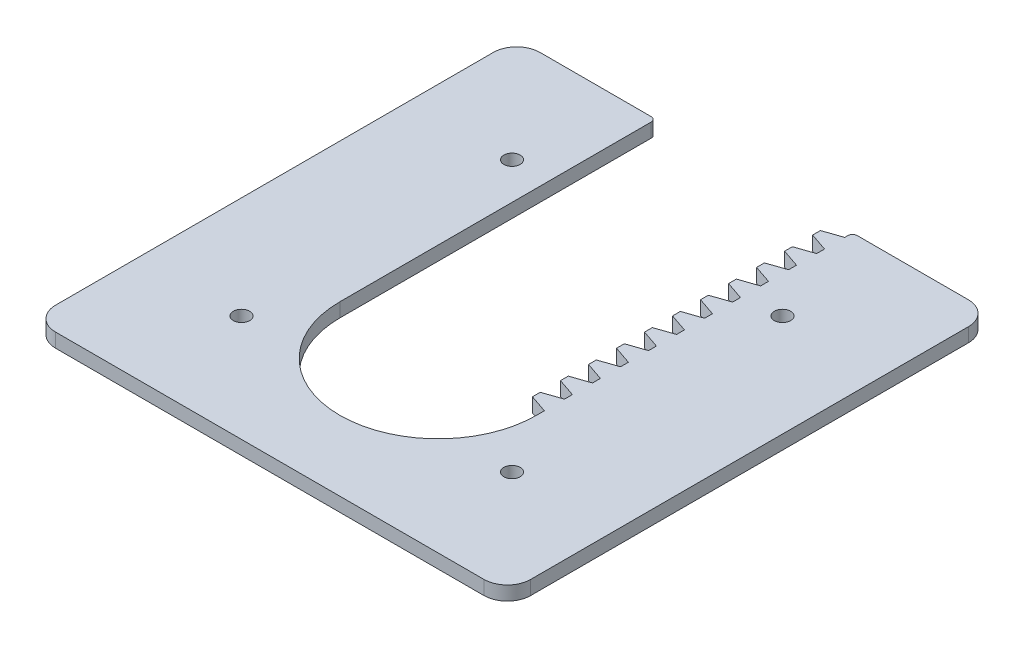
SolidWorks part; units mm, degrees
ref_plane "Front Plane" through (0, 0, 0) normal (0, 0, 1) x (1, 0, 0)
ref_plane "Top Plane" through (0, 0, 0) normal (0, 1, 0) x (1, 0, 0)
ref_plane "Right Plane" through (0, 0, 0) normal (1, 0, 0) x (0, 0, -1)
sketch "Sketch1" plane through (0, 0, 0) normal (0, 1, 0) x (1, 0, 0)
  line L0 (0, 0) -> (0, 21) construction
  line L1 (17.1887, 0) -> (0, 0) construction
  line L2 (21.0585, 3.843) -> (17.1887, 5.1665) construction
  line L3 (17.1887, 5.1665) -> (17.1887, 6.8335) construction
  line L4 (17.1887, 6.8335) -> (21.0585, 8.157) construction
  line L5 (21.0585, 9.843) -> (21.0585, 8.157) construction
  line L6 (21.0585, 9.843) -> (17.1887, 11.1665) construction
  line L7 (17.1887, 11.1665) -> (17.1887, 12.8335) construction
  line L8 (17.1887, 12.8335) -> (21.0585, 14.157) construction
  line L9 (21.0585, 15.843) -> (21.0585, 14.157) construction
  line L10 (21.0585, 15.843) -> (17.1887, 17.1665) construction
  line L11 (17.1887, 17.1665) -> (17.1887, 18.8335) construction
  line L12 (17.1887, 18.8335) -> (21.0585, 20.157) construction
  line L13 (21.0585, 21.843) -> (21.0585, 20.157) construction
  line L14 (21.0585, 21.843) -> (17.1887, 23.1665) construction
  line L15 (17.1887, 23.1665) -> (17.1887, 24.8335) construction
  line L16 (17.1887, 24.8335) -> (21.0585, 26.157) construction
  line L17 (21.0585, 27.843) -> (21.0585, 26.157) construction
  line L18 (21.0585, 27.843) -> (17.1887, 29.1665) construction
  line L19 (17.1887, 29.1665) -> (17.1887, 30.8335) construction
  line L20 (17.1887, 30.8335) -> (21.0585, 32.157) construction
  line L21 (21.0585, 33.843) -> (21.0585, 32.157) construction
  line L22 (21.0585, 33.843) -> (17.1887, 35.1665) construction
  line L23 (17.1887, 35.1665) -> (17.1887, 36.8335) construction
  line L24 (17.1887, 36.8335) -> (21.0585, 38.157) construction
  line L25 (21.0585, 39.843) -> (21.0585, 38.157) construction
  line L26 (21.0585, 39.843) -> (17.1887, 41.1665) construction
  line L27 (17.1887, 41.1665) -> (17.1887, 42.8335) construction
  line L28 (17.1887, 42.8335) -> (21.0585, 44.157) construction
  line L29 (21.0585, 45.843) -> (21.0585, 44.157) construction
  line L30 (21.0585, 45.843) -> (17.1887, 47.1665) construction
  line L31 (17.1887, 47.1665) -> (17.1887, 48.8335) construction
  line L32 (17.1887, 48.8335) -> (21.0585, 50.157) construction
  line L33 (21.0585, 51.843) -> (21.0585, 50.157) construction
  line L34 (21.0585, 51.843) -> (17.1887, 53.1665) construction
  line L35 (17.1887, 53.1665) -> (17.1887, 54.8335) construction
  line L36 (17.1887, 54.8335) -> (21.0585, 56.157) construction
  line L37 (21.0585, 57.843) -> (21.0585, 56.157) construction
  line L38 (21.0585, 57.843) -> (17.1887, 59.1665) construction
  line L39 (17.1887, 59.1665) -> (17.1887, 60.8335) construction
  line L40 (17.1887, 60.8335) -> (21.0585, 62.157) construction
  line L41 (21.0585, 62.157) -> (21.0585, 62.843) construction
  line L42 (45.8722, 63.843) -> (22.0585, 63.843) construction
  line L43 (50.8722, -34.9014) -> (50.8722, 58.843) construction
  line L44 (45.8722, -39.9014) -> (-45.8722, -39.9014) construction
  line L45 (-50.8722, 58.843) -> (-50.8722, -34.9014) construction
  line L46 (-45.8722, 63.843) -> (-22.0585, 63.843) construction
  line L47 (-21.0585, -3.843) -> (-21.0585, 62.843) construction
  line L48 (21.0585, -2.157) -> (21.0585, -3.843) construction
  line L49 (21.0585, -2.157) -> (17.1887, -0.8335) construction
  line L50 (17.1887, -0.8335) -> (17.1887, 0.8335) construction
  line L51 (17.1887, 0.8335) -> (21.0585, 2.157) construction
  line L52 (21.0585, 3.843) -> (21.0585, 2.157) construction
  line L53 (21.0585, 3.843) -> (17.1887, 5.1665)
  line L54 (17.1887, 5.1665) -> (17.1887, 6.8335)
  line L55 (17.1887, 6.8335) -> (21.0585, 8.157)
  line L56 (21.0585, 9.843) -> (21.0585, 8.157)
  line L57 (21.0585, 9.843) -> (17.1887, 11.1665)
  line L58 (17.1887, 11.1665) -> (17.1887, 12.8335)
  line L59 (17.1887, 12.8335) -> (21.0585, 14.157)
  line L60 (21.0585, 15.843) -> (21.0585, 14.157)
  line L61 (21.0585, 15.843) -> (17.1887, 17.1665)
  line L62 (17.1887, 17.1665) -> (17.1887, 18.8335)
  line L63 (17.1887, 18.8335) -> (21.0585, 20.157)
  line L64 (21.0585, 21.843) -> (21.0585, 20.157)
  line L65 (21.0585, 21.843) -> (17.1887, 23.1665)
  line L66 (17.1887, 23.1665) -> (17.1887, 24.8335)
  line L67 (17.1887, 24.8335) -> (21.0585, 26.157)
  line L68 (21.0585, 27.843) -> (21.0585, 26.157)
  line L69 (21.0585, 27.843) -> (17.1887, 29.1665)
  line L70 (17.1887, 29.1665) -> (17.1887, 30.8335)
  line L71 (17.1887, 30.8335) -> (21.0585, 32.157)
  line L72 (21.0585, 33.843) -> (21.0585, 32.157)
  line L73 (21.0585, 33.843) -> (17.1887, 35.1665)
  line L74 (17.1887, 35.1665) -> (17.1887, 36.8335)
  line L75 (17.1887, 36.8335) -> (21.0585, 38.157)
  line L76 (21.0585, 39.843) -> (21.0585, 38.157)
  line L77 (21.0585, 39.843) -> (17.1887, 41.1665)
  line L78 (17.1887, 41.1665) -> (17.1887, 42.8335)
  line L79 (17.1887, 42.8335) -> (21.0585, 44.157)
  line L80 (21.0585, 45.843) -> (21.0585, 44.157)
  line L81 (21.0585, 45.843) -> (17.1887, 47.1665)
  line L82 (17.1887, 47.1665) -> (17.1887, 48.8335)
  line L83 (17.1887, 48.8335) -> (21.0585, 50.157)
  line L84 (21.0585, 51.843) -> (21.0585, 50.157)
  line L85 (21.0585, 51.843) -> (17.1887, 53.1665)
  line L86 (17.1887, 53.1665) -> (17.1887, 54.8335)
  line L87 (17.1887, 54.8335) -> (21.0585, 56.157)
  line L88 (21.0585, 57.843) -> (21.0585, 56.157)
  line L89 (21.0585, 57.843) -> (17.1887, 59.1665)
  line L90 (17.1887, 59.1665) -> (17.1887, 60.8335)
  line L91 (17.1887, 60.8335) -> (21.0585, 62.157)
  line L92 (21.0585, 62.157) -> (21.0585, 62.843)
  line L93 (45.8722, 63.843) -> (22.0585, 63.843)
  line L94 (50.8722, -34.9014) -> (50.8722, 58.843)
  line L95 (45.8722, -39.9014) -> (-45.8722, -39.9014)
  line L96 (-50.8722, 58.843) -> (-50.8722, -34.9014)
  line L97 (-45.8722, 63.843) -> (-22.0585, 63.843)
  line L98 (-21.0585, -3.843) -> (-21.0585, 62.843)
  line L99 (21.0585, -2.157) -> (21.0585, -3.843)
  line L100 (21.0585, -2.157) -> (17.1887, -0.8335)
  line L101 (17.1887, -0.8335) -> (17.1887, 0.8335)
  line L102 (17.1887, 0.8335) -> (21.0585, 2.157)
  line L103 (21.0585, 3.843) -> (21.0585, 2.157)
  line L104 (0, 63.843) -> (0, -39.9014) construction
  line L105 (-51.8722, 11.9708) -> (51.8722, 11.9708) construction
  line L106 (0, 11.9708) -> (-51.8722, -39.9014) construction
  line L107 (51.8722, -24.9014) -> (-51.8722, -24.9014) construction
  line L108 (-36.8722, -39.9014) -> (-36.8722, 63.843) construction
  line L109 (36.8722, -39.9014) -> (36.8722, 63.843) construction
  line L110 (45.8722, -39.9014) -> (51.8722, -39.9014) construction
  line L111 (51.8722, -39.9014) -> (51.8722, 63.843) construction
  line L112 (51.8722, 63.843) -> (-51.8722, 63.843) construction
  line L113 (17.1887, 60) -> (0, 60) construction
  line L114 (-51.8722, 63.843) -> (-51.8722, -39.9014) construction
  line L115 (-51.8722, -39.9014) -> (-45.8722, -39.9014) construction
  circle A0 centre (0, 0) radius 21 construction
  circle A1 centre (0, 60) radius 21 construction
  arc A2 (22.0585, 63.843) -> (21.0585, 62.843) centre (22.0585, 62.843) ccw construction
  arc A3 (50.8722, 58.843) -> (45.8722, 63.843) centre (45.8722, 58.843) ccw construction
  arc A4 (45.8722, -39.9014) -> (50.8722, -34.9014) centre (45.8722, -34.9014) ccw construction
  arc A5 (-50.8722, -34.9014) -> (-45.8722, -39.9014) centre (-45.8722, -34.9014) ccw construction
  arc A6 (-45.8722, 63.843) -> (-50.8722, 58.843) centre (-45.8722, 58.843) ccw construction
  arc A7 (-21.0585, 62.843) -> (-22.0585, 63.843) centre (-22.0585, 62.843) ccw construction
  arc A8 (-21.0585, -3.843) -> (21.0585, -3.843) centre (0, -3.843) ccw construction
  arc A9 (22.0585, 63.843) -> (21.0585, 62.843) centre (22.0585, 62.843) ccw
  arc A10 (50.8722, 58.843) -> (45.8722, 63.843) centre (45.8722, 58.843) ccw
  arc A11 (45.8722, -39.9014) -> (50.8722, -34.9014) centre (45.8722, -34.9014) ccw
  arc A12 (-50.8722, -34.9014) -> (-45.8722, -39.9014) centre (-45.8722, -34.9014) ccw
  arc A13 (-45.8722, 63.843) -> (-50.8722, 58.843) centre (-45.8722, 58.843) ccw
  arc A14 (-21.0585, 62.843) -> (-22.0585, 63.843) centre (-22.0585, 62.843) ccw
  arc A15 (-21.0585, -3.843) -> (21.0585, -3.843) centre (0, -3.843) ccw
  circle A16 centre (28.9653, -16.9946) radius 1.75 construction
  circle A17 centre (-28.9653, -16.9946) radius 1.75 construction
  circle A18 centre (-28.9653, 40.9361) radius 1.75 construction
  circle A19 centre (28.9653, 40.9361) radius 1.75 construction
  circle A20 centre (28.9653, -16.9946) radius 1.75
  circle A21 centre (-28.9653, -16.9946) radius 1.75
  circle A22 centre (-28.9653, 40.9361) radius 1.75
  circle A23 centre (28.9653, 40.9361) radius 1.75
  circle A24 centre (0, 60) radius 21 construction
sketch "Sketch2" plane through (0, 0, 0) normal (0, 0, 1) x (1, 0, 0)
  line L0 (0, 0) -> (0, 3) construction
  line L1 (-50.8722, 0) -> (50.8722, 0)
  line L2 (-50.8722, 0) -> (-50.8722, 3)
  line L3 (-50.8722, 3) -> (50.8722, 3)
  line L4 (50.8722, 0) -> (50.8722, 3)
  line L5 (-50.8722, 3) -> (-51.8722, 3) construction
  line L6 (-51.8722, 3) -> (-51.8722, 3.75) construction
  line L7 (-51.8722, 3.75) -> (51.8722, 3.75) construction
  line L8 (51.8722, 3.75) -> (51.8722, 3) construction
  line L9 (51.8722, 3) -> (50.8722, 3) construction
  line L10 (50.8722, 0) -> (51.8722, 0) construction
  line L11 (51.8722, 0) -> (51.8722, -0.75) construction
  line L12 (51.8722, -0.75) -> (-51.8722, -0.75) construction
  line L13 (-51.8722, -0.75) -> (-51.8722, 0) construction
  line L14 (-51.8722, 0) -> (-50.8722, 0) construction
  line L15 (59.5, 48.3) -> (59.5, 45.3) construction
  dimension "D2" = 0.75
extrude "Boss-Extrude1" add sketch "Sketch1" along normal up to vertex (3 mm away) up to point (-50.8722, 3, 0)
ref_plane "edge" through (0, 0, -63.843) normal (0, 0, 1) x (1, 0, 0)
